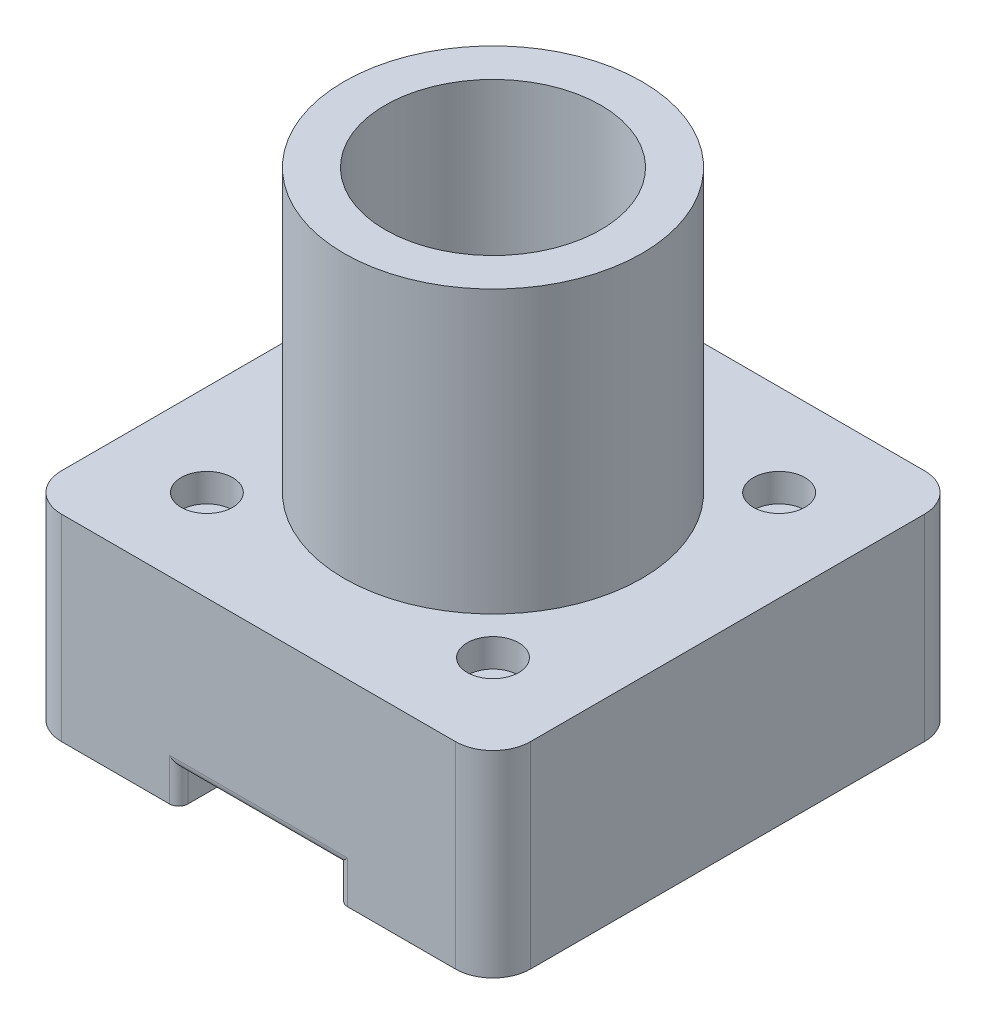
SolidWorks part; units mm, degrees
ref_plane "Front Plane" through (0, 0, 0) normal (0, 0, 1) x (1, 0, 0)
ref_plane "Top Plane" through (0, 0, 0) normal (0, 1, 0) x (1, 0, 0)
ref_plane "Right Plane" through (0, 0, 0) normal (1, 0, 0) x (0, 0, -1)
sketch "Sketch4" plane through (0, 0, 0) normal (0, 1, 0) x (1, 0, 0)
  line L0 (15.25, -15.25) -> (-15.25, -15.25) construction
  line L1 (21, -25) -> (-21, -25)
  line L2 (25, -21) -> (25, 21)
  line L3 (21, 25) -> (-21, 25)
  line L4 (-25, -21) -> (-25, 21)
  line L5 (25, -25) -> (-25, 25) construction
  line L6 (25, 25) -> (-25, -25) construction
  line L7 (-15.25, -15.25) -> (-15.25, 15.25) construction
  line L8 (-15.5, -19.5) -> (15.5, -19.5)
  line L9 (-19.5, -15.5) -> (-19.5, 15.5)
  line L10 (-15.5, 19.5) -> (15.5, 19.5)
  line L11 (19.5, -15.5) -> (19.5, 15.5)
  line L12 (-19.5, -19.5) -> (19.5, 19.5) construction
  line L13 (-19.5, 19.5) -> (19.5, -19.5) construction
  line L14 (0, 25) -> (0, -19.5) construction
  line L15 (-15.25, 15.25) -> (15.25, 15.25) construction
  line L20 (0, -19.5) -> (0, -25) construction
  line L21 (-5.5, 22) -> (5.5, 22)
  line L22 (15.25, 15.25) -> (15.25, -15.25) construction
  line L23 (-5.5, 22) -> (-5.5, 17.1391)
  line L24 (-5.5, 17.1391) -> (5.5, 17.1391)
  line L25 (5.5, 22) -> (5.5, 17.1391)
  line L26 (-5.5, 22) -> (5.5, 17.1391) construction
  line L27 (-5.5, 17.1391) -> (5.5, 22) construction
  line L30 (-8.5, -19.5) -> (8.5, -19.5)
  line L31 (-8.5, -19.5) -> (-8.5, -25)
  line L32 (-8.5, -25) -> (8.5, -25)
  line L33 (8.5, -19.5) -> (8.5, -25)
  line L34 (-8.5, -19.5) -> (8.5, -25) construction
  line L35 (-8.5, -25) -> (8.5, -19.5) construction
  circle A0 centre (0, 0) radius 13.7
  circle A1 centre (15.25, -15.25) radius 1.5
  arc A2 (-25, -21) -> (-21, -25) centre (-21, -21) ccw
  arc A3 (25, -21) -> (21, -25) centre (21, -21) cw
  arc A4 (21, 25) -> (25, 21) centre (21, 21) cw
  arc A5 (-21, 25) -> (-25, 21) centre (-21, 21) ccw
  arc A6 (19.5, 15.5) -> (15.5, 19.5) centre (15.5, 15.5) ccw
  arc A7 (19.5, -15.5) -> (15.5, -19.5) centre (15.5, -15.5) cw
  arc A8 (-15.5, -19.5) -> (-19.5, -15.5) centre (-15.5, -15.5) cw
  arc A9 (-19.5, 15.5) -> (-15.5, 19.5) centre (-15.5, 15.5) cw
  circle A12 centre (0, 0) radius 11.5
  circle A13 centre (0, 0) radius 15.875
  circle A14 centre (-15.25, -15.25) radius 1.5
  circle A15 centre (-15.25, 15.25) radius 1.5
  circle A16 centre (15.25, 15.25) radius 1.5
  circle A17 centre (0, 0) radius 18
  circle A18 centre (-15.25, -15.25) radius 2.75
  circle A19 centre (15.25, -15.25) radius 2.75
  circle A20 centre (15.25, 15.25) radius 2.75
  circle A21 centre (-15.25, 15.25) radius 2.75
  point P43 (0, 19.5696)
  point P58 (0, -22.25)
  dimension "D2" = 4
  dimension "D5" = 4
  dimension "D8" = 23
  dimension "D9" = 31.75
  dimension "D10" = 50
  dimension "D4" = 27.4
  dimension "D11" = 3
  dimension "D13" = 11
  dimension "D6" = 36
  dimension "D14" = 5.5
  dimension "D3" = 39
  dimension "D7" = 2.5
  dimension "D12" = 30.5
  dimension "D15" = 17
extrude "Boss-Extrude1" add sketch "Sketch4" against normal blind 16 contours L9 A9 L10 L23 L21 L25 A6 L11 A7 L8 L33 L1 A3 L2 A4 L3 A5 L4 A2 L31 A8 region at (14.75, 0, 24.2929)
extrude "Boss-Extrude2" add sketch "Sketch4<3>" against normal blind 11
sketch "Sketch4<3>" plane through (0, 0, 0) normal (0, 1, 0) x (1, 0, 0) same geometry as "Sketch4"
extrude "Boss-Extrude3" add sketch "Sketch4<4>" against normal blind 7 separate body contours A0
sketch "Sketch4<4>" plane through (0, 0, 0) normal (0, 1, 0) x (1, 0, 0) same geometry as "Sketch4"
extrude "Boss-Extrude4" add sketch "Sketch4<5>" along normal blind 5 contours L4 A5 L3 A4 L2 A3 L1 A2
sketch "Sketch4<5>" plane through (0, 0, 0) normal (0, 1, 0) x (1, 0, 0) same geometry as "Sketch4"
extrude "Boss-Extrude5" add sketch "Sketch4<6>" along normal blind 30 from surface contours A13 starting at face at (0, 5, 0)
sketch "Sketch4<6>" plane through (0, 0, 0) normal (0, 1, 0) x (1, 0, 0) same geometry as "Sketch4"
extrude "Cut-Extrude1" cut sketch "Sketch4<7>" along normal through all and the other way up to next (7 mm away) contours A12
sketch "Sketch4<7>" plane through (0, 0, 0) normal (0, 1, 0) x (1, 0, 0) same geometry as "Sketch4"
extrude "Cut-Extrude4" cut sketch "Sketch4<8>" along normal through all and the other way through all contours A15 | A16 | A1 | A14
sketch "Sketch4<8>" plane through (0, 0, 0) normal (0, 1, 0) x (1, 0, 0) same geometry as "Sketch4"
extrude "Cut-Extrude5" cut sketch "Sketch4<9>" against normal blind 3 from surface contours A18 | A19 | A20 | A21 starting at face at (-15.25, 5, -13.75)
sketch "Sketch4<9>" plane through (0, 0, 0) normal (0, 1, 0) x (1, 0, 0) same geometry as "Sketch4"
extrude "Boss-Extrude6" add sketch "Sketch4<10>" against normal offset from surface (12.5 mm away) 1.5 contours L33 L8 L31 L1 region at (0, 0, 22.25) up to face at (0, -11, 0.0615) offset beyond the face yes
sketch "Sketch4<10>" plane through (0, 0, 0) normal (0, 1, 0) x (1, 0, 0) same geometry as "Sketch4"
fillet "Fillet1" radius 1 6 edges at (8.5, -14.25, 25) (8.5, -14.25, 19.5) (-8.5, -14.25, 25) (-8.5, -14.25, 19.5) (0, -12.5, 25) (0, -12.5, 19.5)
